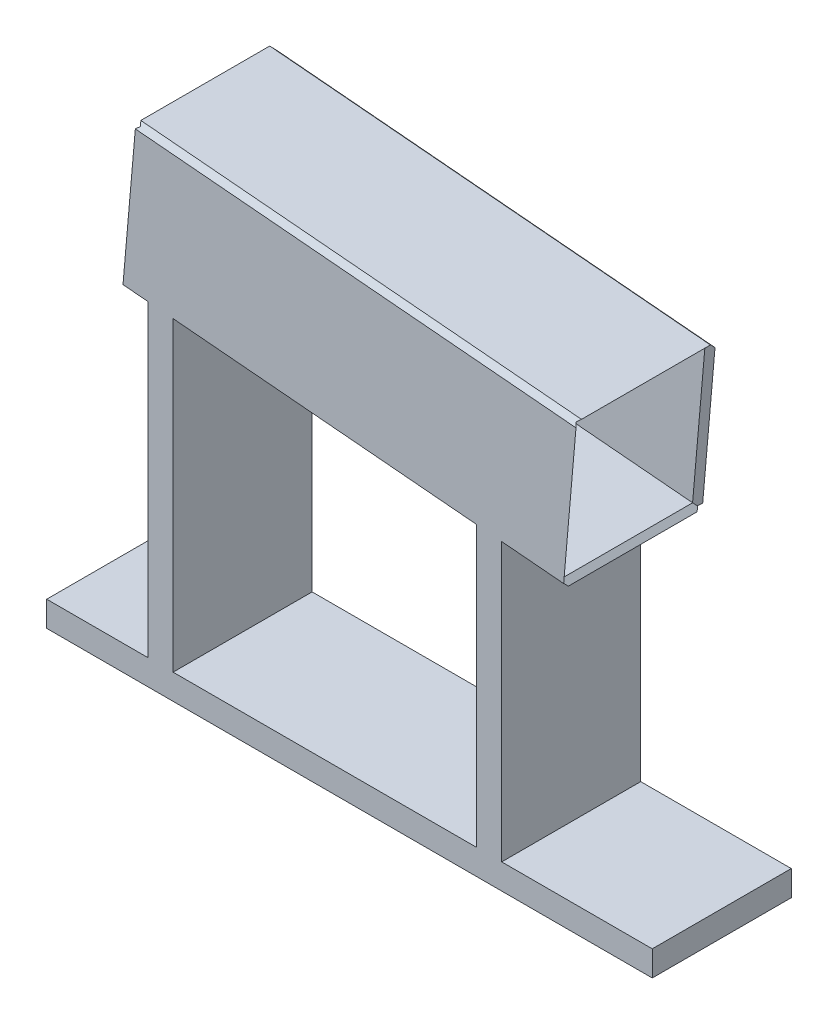
SolidWorks part; units mm, degrees
ref_plane "Front Plane" through (0, 0, 0) normal (0, 0, 1) x (1, 0, 0)
ref_plane "Top Plane" through (0, 0, 0) normal (0, 1, 0) x (1, 0, 0)
ref_plane "Right Plane" through (0, 0, 0) normal (1, 0, 0) x (0, 0, -1)
sketch "Sketch1" plane through (0, 0, 0) normal (0, 0, 1) x (1, 0, 0)
  line L4 (0, 0) -> (-174.3341, 15.2523)
  line L5 (-174.3341, 15.2523) -> (-169.1047, 75.0239)
  line L6 (-169.1047, 75.0239) -> (5.2293, 59.7717)
  line L7 (5.2293, 59.7717) -> (0, 0)
  line L8 (0, 0) -> (38.1353, 0) construction
  dimension "D1" = 175
  dimension "D2" = 60
  dimension "D3" = 85
extrude "Boss-Extrude1" add sketch "Sketch1" along normal blind 55
sketch "Sketch2" plane through (0, 0, 0) normal (0.9962, -0.0872, 0) x (0, 0, -1)
  line L0 (-27.5, 60) -> (-27.5, 0) construction
  line L1 (-53, 58) -> (-2, 58)
  line L2 (-53, 58) -> (-53, 2)
  line L3 (-53, 2) -> (-2, 2)
  line L4 (-2, 58) -> (-2, 2)
  line L5 (-53, 58) -> (-2, 2) construction
  line L6 (-53, 2) -> (-2, 58) construction
  line L7 (-55, 60) -> (0, 60) construction
  line L8 (-55, 0) -> (0, 0) construction
  line L9 (-55, 30) -> (0, 30) construction
  line L10 (-55, 0) -> (-55, 60) construction
  line L11 (0, 0) -> (0, 60) construction
  point P0 (-27.5, 30)
  point P20 (-27.5, 30)
  dimension "D1" = 2
  dimension "D2" = 2
extrude "Cut-Extrude1" cut sketch "Sketch2" against normal through all
sketch "Sketch3" plane through (0, 0, 0) normal (0, 0, 1) x (1, 0, 0)
  line L0 (-164.3341, 14.3774) -> (-164.3341, -105.6226)
  line L1 (-174.3341, 15.2523) -> (0, 0) construction
  line L2 (-164.3341, -105.6226) -> (-154.3341, -105.6226)
  line L3 (-154.3341, -105.6226) -> (-154.3341, 13.5025)
  line L4 (-34.3341, 3.0038) -> (-34.3341, -105.6226)
  line L5 (-34.3341, -105.6226) -> (-24.3341, -105.6226)
  line L6 (-24.3341, -105.6226) -> (-24.3341, 2.129)
  line L7 (-24.3341, 2.129) -> (-34.3341, 3.0038)
  line L8 (0, 0) -> (5.2293, 59.7717)
  line L9 (5.2293, 59.7717) -> (-169.1047, 75.0239)
  line L10 (-169.1047, 75.0239) -> (-174.3341, 15.2523)
  line L11 (-174.3341, 15.2523) -> (0, 0)
  line L15 (-164.3341, 14.3774) -> (-154.3341, 13.5025)
  line L16 (-154.3341, -105.6226) -> (-34.3341, -105.6226) construction
  dimension "D1" = 10
  dimension "D2" = 120
  dimension "D4" = 10
  dimension "D5" = 10
  dimension "D6" = 120
  dimension "D3" = 0
extrude "Boss-Extrude4" add sketch "Sketch3" along normal blind 55
sketch "Sketch7" plane through (0, -105.6226, 0) normal (0, -1, 0) x (1, 0, 0)
  line L0 (-204.3341, 55) -> (35.2293, 55)
  line L1 (35.2293, 55) -> (35.2293, 0)
  line L2 (35.2293, 0) -> (-204.3341, 0)
  line L3 (-204.3341, 0) -> (-204.3341, 55)
  line L4 (-154.3341, 55) -> (-34.3341, 55) construction
  line L6 (-154.3341, 0) -> (-34.3341, 0) construction
  line L7 (5.2293, 55) -> (5.2293, 0) construction
  line L8 (-174.3341, 55) -> (-174.3341, 0) construction
  point P13 (35.2293, 27.5)
  dimension "D3" = 30
  dimension "D4" = 30
extrude "Boss-Extrude5" add sketch "Sketch7" along normal blind 10
chamfer "Chamfer6" distance 2 angle 45 8 edges at (-171.7194, 45.1381, 53) (-169.279, 73.0315, 27.5) (-171.7194, 45.1381, 2) (-174.1598, 17.2446, 27.5) (0.1743, 1.9924, 27.5) (2.6147, 29.8858, 2) (2.6147, 29.8858, 53) (5.055, 57.7793, 27.5)
chamfer "Chamfer7" distance 2 angle 45 8 edges at (-169.3341, 14.8148, 0) (-169.3341, 14.8148, 55) (-12.167, 1.0645, 55) (-12.167, 1.0645, 0) (-94.3341, 8.2532, 0) (-94.3341, 8.2532, 55) (-81.9377, 67.3978, 0) (-81.9377, 67.3978, 55)
fillet "Fillet4" radius 5 1 edges at (-24.3341, 2.129, 27.5)
fillet "Fillet5" radius 5 1 edges at (-34.3341, 3.0038, 27.5)
fillet "Fillet6" radius 5 1 edges at (-154.3341, 13.5025, 27.5)
fillet "Fillet7" radius 5 1 edges at (-164.3341, 14.3774, 27.5)
